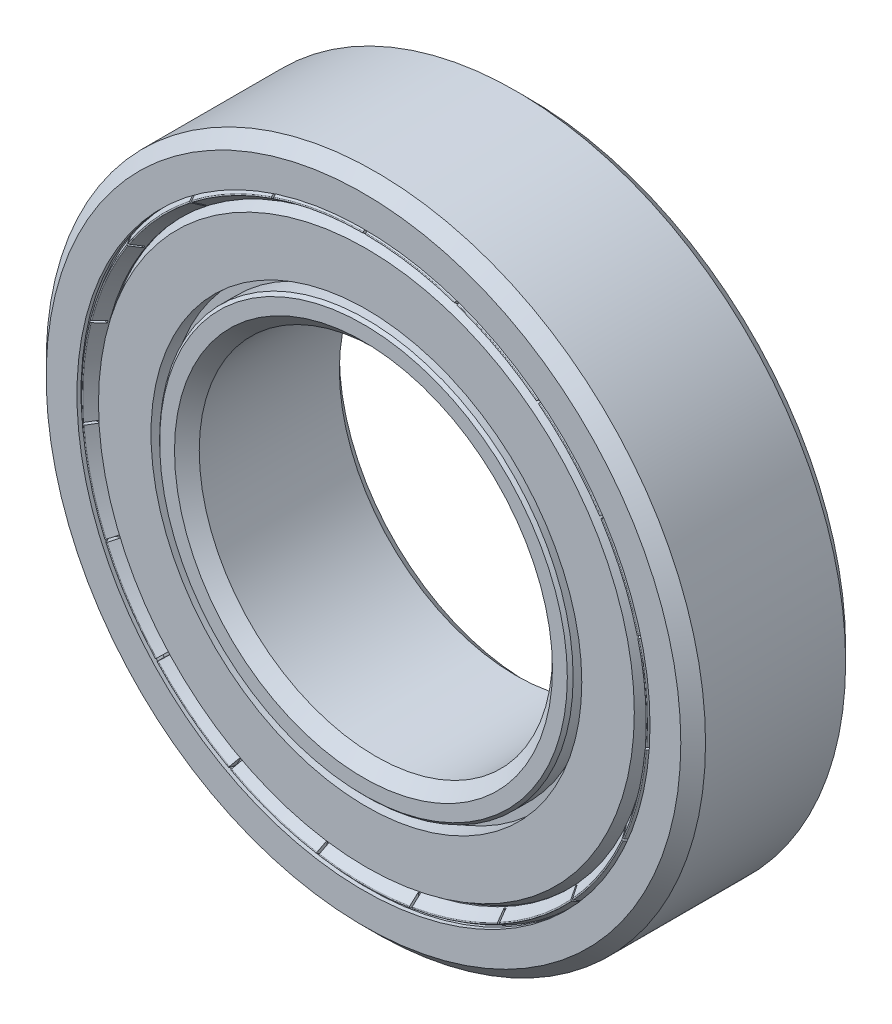
SolidWorks part; units mm, degrees
material "Chrome Stainless Steel"
ref_plane "Front Plane" through (0, 0, 0) normal (0, 0, 1) x (1, 0, 0)
ref_plane "Top Plane" through (0, 0, 0) normal (0, 1, 0) x (1, 0, 0)
ref_plane "Right Plane" through (0, 0, 0) normal (1, 0, 0) x (0, 0, -1)
sketch "Sketch1" plane through (0, 0, 0) normal (0, 0, 1) x (1, 0, 0)
  circle A0 centre (0, 0) radius 7.5
  circle A1 centre (0, 0) radius 14
  dimension "OD" = 28
  dimension "ID" = 15
sketch "Sketch2" plane through (0, 0, 0) normal (1, 0, 0) x (0, 0, -1)
  line L0 (-3.5, 14) -> (3.5, 14)
  line L1 (-3.5, 7.5) -> (-3.5, -7.5) construction
  line L2 (3.5, 14) -> (3.5, -14) construction
  line L3 (-3.5, 0) -> (3.5, 0) construction
  line L6 (0, 14) -> (0, 7.5) construction
  circle A0 centre (0, 10.75) radius 2.275 construction
  point P8 (0, 14)
  dimension "Approx. Ball Dia." = 4.55
  dimension "Width" = 7
  dimension "For Shaft Diameter" = 15
  dimension "For Housing ID" = 28
sketch "Sketch3" plane through (0, 0, 0) normal (1, 0, 0) x (0, 0, -1)
  line L0 (0, 0) -> (0, 15) construction
  line L1 (-3.5, 7.5) -> (-3.5, -7.5) construction
  line L2 (2.975, 14) -> (-2.975, 14)
  line L3 (-2.975, 14) -> (-3.5, 13.475)
  line L4 (-3.5, 13.475) -> (-3.5, 12.1679)
  line L5 (-3.5, 12.1679) -> (-3.325, 12.1679)
  line L6 (-3.325, 12.1679) -> (-3.325, 12.5965)
  line L7 (-3.325, 12.5965) -> (-3.2013, 12.7202)
  line L8 (-3.2013, 12.7202) -> (-1.1375, 12.7202)
  line L10 (-3.5, 14) -> (3.5, 14) construction
  line L12 (-3.325, 12.5965) -> (-3.325, 13.025) construction
  line L13 (3.2013, 12.7202) -> (1.1375, 12.7202)
  line L14 (3.325, 12.5965) -> (3.2013, 12.7202)
  line L15 (3.325, 12.1679) -> (3.325, 12.5965)
  line L16 (3.5, 12.1679) -> (3.325, 12.1679)
  line L17 (3.5, 13.475) -> (3.5, 12.1679)
  line L18 (2.975, 14) -> (3.5, 13.475)
  line L19 (2.975, 7.5) -> (-2.975, 7.5)
  line L20 (-2.975, 7.5) -> (-3.5, 8.025)
  line L21 (-3.5, 8.025) -> (-3.5, 8.656)
  line L22 (-3.5, 8.656) -> (-3.3763, 8.7798)
  line L23 (-3.3763, 8.7798) -> (-1.1375, 8.7798)
  line L25 (3.3763, 8.7798) -> (1.1375, 8.7798)
  line L26 (3.5, 8.656) -> (3.3763, 8.7798)
  line L27 (3.5, 8.025) -> (3.5, 8.656)
  line L28 (2.975, 7.5) -> (3.5, 8.025)
  circle A2 centre (0, 10.75) radius 2.275 construction
  arc A3 (-1.1375, 12.7202) -> (1.1375, 12.7202) centre (0, 10.75) cw
  arc A4 (-1.1375, 8.7798) -> (1.1375, 8.7798) centre (0, 10.75) ccw
  point P5 (0, 13.025)
  point P31 (0, 14)
  point P37 (0, 7.5)
  dimension "D1" = 45
  dimension "D2" = 0.175
  dimension "D3" = 2.275
  dimension "D4" = 0.525
revolve "Revolve1" add sketch "Sketch3" angle 360 about L3
sketch "Sketch4" plane through (0, 0, 0) normal (1, 0, 0) x (0, 0, -1)
  line L0 (0, 13.025) -> (0, 8.475)
  line L1 (0, 14) -> (0, 7.5) construction
  circle A0 centre (0, 10.75) radius 2.275 construction
  arc A1 (0, 8.475) -> (0, 13.025) centre (0, 10.75) cw
revolve "Revolve2" add sketch "Sketch4" angle 360 about L6
pattern_circular "CirPattern1" count 10 over 360 about axis through (0, 0, 3.5) along (0, 0, -1) of bodies 106
sketch "Sketch5" plane through (0, 0, 0) normal (1, 0, 0) x (0, 0, -1)
  line L0 (-2.275, 10.75) -> (-2.275, 8.7798) construction
  line L1 (-3.3763, 8.7798) -> (-1.1375, 8.7798) construction
  line L3 (-2.275, 8.7798) -> (-2.6421, 8.7798)
  line L4 (-2.6421, 8.7798) -> (-2.6421, 9.1469)
  line L5 (-2.6421, 9.1469) -> (-3.3763, 9.1469)
  line L6 (-3.3763, 9.1469) -> (-3.3763, 11.377)
  line L7 (-3.3763, 11.377) -> (-2.6421, 11.8008)
  line L8 (-2.6421, 11.8008) -> (-2.275, 11.8008)
  line L9 (-2.275, 11.8008) -> (-2.275, 8.7798)
  line L10 (0, 10.75) -> (0, 14) construction
  line L11 (2.6421, 11.8008) -> (2.275, 11.8008)
  line L12 (3.3763, 11.377) -> (2.6421, 11.8008)
  line L13 (3.3763, 9.1469) -> (3.3763, 11.377)
  line L14 (2.6421, 9.1469) -> (3.3763, 9.1469)
  line L15 (2.6421, 8.7798) -> (2.6421, 9.1469)
  line L16 (2.275, 8.7798) -> (2.6421, 8.7798)
  line L17 (2.275, 11.8008) -> (2.275, 8.7798)
  line L18 (-3.3763, 11.377) -> (-3.0092, 11.377) construction
  line L19 (-3.0092, 11.377) -> (-2.6421, 11.377) construction
  line L20 (-2.6421, 11.377) -> (-2.275, 11.377) construction
  line L21 (-2.6421, 11.8008) -> (-2.6421, 12.1679) construction
  circle A0 centre (0, 10.75) radius 2.275 construction
  dimension "D1" = 30
revolve "Revolve3" add sketch "Sketch5" angle 360 about L3
sketch "Sketch6" plane through (0, 0, 0) normal (1, 0, 0) x (0, 0, -1)
  line L0 (-2.8961, 12.1679) -> (-3.1937, 12.1679)
  line L1 (-3.1937, 12.1679) -> (-3.5, 11.9911)
  line L2 (-3.5, 11.9911) -> (-3.0011, 11.6418)
  line L4 (-3.3763, 11.377) -> (-2.6421, 11.8008) construction
  line L5 (-2.8961, 11.6542) -> (-2.8961, 12.1679)
  line L6 (-3.5, 12.1679) -> (-3.325, 12.1679) construction
  line L7 (-3.0011, 11.6418) -> (-2.9661, 11.6418)
  line L8 (-2.9661, 11.6418) -> (-2.8961, 11.6542)
  line L9 (-3.5, 13.475) -> (-3.5, -13.475) construction
  line L11 (-2.9661, 11.6418) -> (-2.9311, 11.6418) construction
  line L12 (-2.9311, 11.6418) -> (-2.8961, 11.6418) construction
  point P27 (-3.0449, 12.1679)
  dimension "D1" = 30
  dimension "D3" = 10
  dimension "D2" = 35
  dimension "D4" = 0.035
  dimension "D5" = 0.3062
revolve "Revolve4" add sketch "Sketch6" angle 360 about L3
fillet "Fillet1" radius 0.035 1 edges at (11.9911, 0, 3.5)
sketch "Sketch7" plane through (0, 0, 0) normal (0, 0, 1) x (1, 0, 0)
  line L0 (-0.05, 12.1679) -> (-0.05, 12.2679)
  line L1 (-0.05, 12.1679) -> (0.05, 12.1679) construction
  line L2 (-0.05, 12.1679) -> (-0.05, 11.6418)
  line L3 (-0.05, 11.6418) -> (0.05, 11.6418) construction
  line L4 (0.05, 12.1679) -> (0.05, 11.6418)
  line L5 (-0.05, 12.2679) -> (0.05, 12.2679)
  line L6 (0.05, 12.2679) -> (0.05, 12.1679)
  line L7 (-0.05, 11.6418) -> (-0.05, 11.5418)
  line L8 (-0.05, 11.5418) -> (0.05, 11.5418)
  line L9 (0.05, 11.5418) -> (0.05, 11.6418)
  dimension "D1" = 0.1
extrude "Cut-Extrude1" cut sketch "Sketch7" along normal through all from vertex starting at point (0, 12.1679, 3.0449)
pattern_circular "CirPattern2" count 19 over 360 about axis through (0, 0, 3.5) along (0, 0, -1) of "Cut-Extrude1"
mirror "Mirror1" about plane through (0, 0, 0) normal (0, 0, 1) of bodies 120
equation "\"Approx. Ball Dia.@Sketch2\"=( \"OD@Sketch1\" - \"ID@Sketch1\" )  * .5 * .7"
equation "\"D2@Sketch3\"=\"Width@Sketch2\"*.025"
equation "\"D3@Sketch3\"=\"Approx. Ball Dia.@Sketch2\"*.5"
equation "\"D4@Sketch3\"=\"Width@Sketch2\"*.075"
equation "\"Approx No of Balls\"= ( pi * \"OD@Sketch1\" ) * .5 / \"Approx. Ball Dia.@Sketch2\""
equation "\"D1@CirPattern1\"=\"Approx No of Balls\""
equation "\"D4@Sketch6\"=\"D2@Sketch3\"*.2"
equation "\"D1@CirPattern2\"=\"Approx No of Balls\"*2"
equation "\"D5@Sketch6\"=\"D2@Sketch3\"*1.75"
equation "\"D1@Fillet1\"=\"d4@sketch6\""
